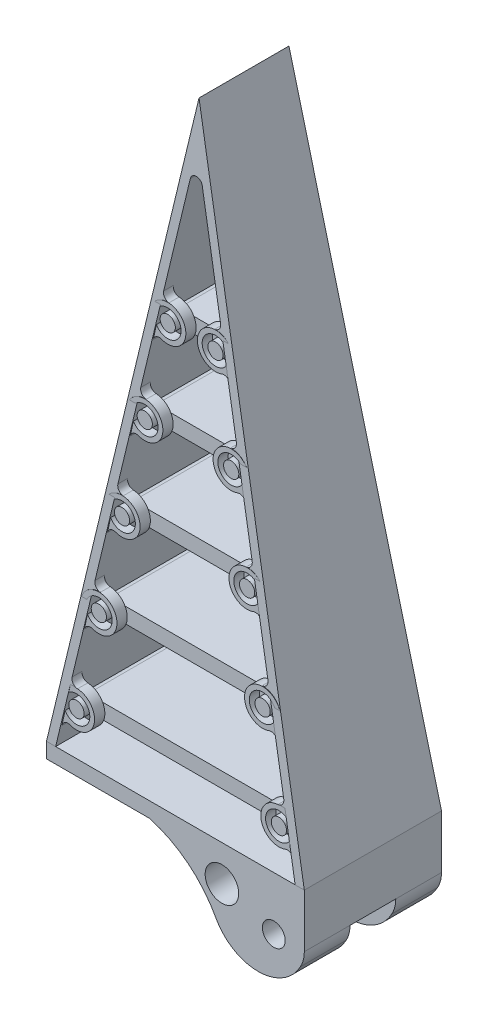
SolidWorks part; units mm, degrees
ref_plane "Ebene vorne" through (0, 0, 0) normal (0, 0, 1) x (1, 0, 0)
ref_plane "Ebene oben" through (0, 0, 0) normal (0, 1, 0) x (1, 0, 0)
ref_plane "Ebene rechts" through (0, 0, 0) normal (1, 0, 0) x (0, 0, -1)
ref_plane "Ebene7" through (0, 0, 9) normal (0, 0, 1) x (1, 0, 0)
ref_plane "Ebene8" through (17, 0, 0) normal (1, 0, 0) x (0, 0, -1)
sketch "Skizze1" plane through (0, 0, 0) normal (0, 0, 1) x (1, 0, 0)
  line L0 (0, 0) -> (16.9111, -80)
  line L1 (16.9111, -80) -> (15.7111, -80)
  line L2 (15.7111, -80) -> (0, -5.6767)
  line L3 (0, -5.6767) -> (-15.7111, -80)
  line L4 (-15.7111, -80) -> (-16.9111, -80)
  line L5 (-16.9111, -80) -> (0, 0)
  point P2 (-16.3111, -80)
  dimension "D1" = 1.2
  dimension "D2" = 1.2
  dimension "D3" = 23.872
  dimension "D4" = 80
extrude "Aufsatz-Linear austragen4" add sketch "Skizze1" along normal blind 18
sketch "Skizze11" plane through (17, 0, 0) normal (1, 0, 0) x (0, 0, -1)
  line L0 (-18, -80) -> (-14.9, 0)
  line L1 (-18, 0) -> (0, 0) construction
  line L2 (-14.9, 0) -> (-18, 0)
  line L3 (-18, 0) -> (-18, -80)
  line L4 (0, -80) -> (-3.1, 0)
  line L5 (-3.1, 0) -> (0, 0)
  line L6 (0, 0) -> (0, -80)
  dimension "D1" = 3.1
  dimension "D2" = 3.1
extrude "Schnitt-Linear austragen1" cut sketch "Skizze11" against normal through all
sketch "Skizze6" plane through (0, 0, 9) normal (0, 0, 1) x (1, 0, 0)
  line L1 (0, -5.6767) -> (-15.7111, -80) construction
  line L2 (15.7111, -80) -> (0, -5.6767) construction
  line L8 (3.1325, -25.6767) -> (-3.1325, -25.6767)
  line L11 (-3.1325, -27.6767) -> (3.1325, -27.6767)
  arc A0 (-3.1325, -25.6767) -> (-3.1325, -27.6767) centre (-3.1325, -26.6767) ccw
  arc A1 (3.1325, -25.6767) -> (3.1325, -27.6767) centre (3.1325, -26.6767) cw
  point P4 (-4.1325, -26.6767)
  point P9 (4.1325, -26.6767)
  dimension "D3" = 0.3
  dimension "D1" = 20
  dimension "D2" = 2
  dimension "D4" = 0.3
extrude "Aufsatz-Linear austragen5" add sketch "Skizze6" along normal blind 5.37 and the other way blind 5.37
sketch "Skizze7" plane through (0, 0, 9) normal (0, 0, 1) x (1, 0, 0)
  line L9 (5.6692, -37.6767) -> (-5.6692, -37.6767)
  line L12 (-5.6692, -39.6767) -> (5.6692, -39.6767)
  line L13 (-3.1325, -27.6767) -> (3.1325, -27.6767) construction
  line L14 (0, -5.6767) -> (-15.7111, -80) construction
  line L15 (15.7111, -80) -> (0, -5.6767) construction
  arc A0 (-5.6692, -37.6767) -> (-5.6692, -39.6767) centre (-5.6692, -38.6767) ccw
  arc A1 (5.6692, -37.6767) -> (5.6692, -39.6767) centre (5.6692, -38.6767) cw
  point P3 (-6.6692, -38.6767)
  point P10 (6.6692, -38.6767)
  dimension "D3" = 0.3
  dimension "D1" = 10
  dimension "D2" = 2
  dimension "D4" = 0.3
extrude "Aufsatz-Linear austragen6" add sketch "Skizze7" along normal blind 5.85 and the other way blind 5.85
sketch "Skizze8" plane through (0, 0, 9) normal (0, 0, 1) x (1, 0, 0)
  line L9 (8.2059, -49.6767) -> (-8.2059, -49.6767)
  line L12 (-8.2059, -51.6767) -> (8.2059, -51.6767)
  line L13 (-5.6692, -39.6767) -> (5.6692, -39.6767) construction
  line L14 (0, -5.6767) -> (-15.7111, -80) construction
  line L15 (15.7111, -80) -> (0, -5.6767) construction
  arc A0 (-8.2059, -49.6767) -> (-8.2059, -51.6767) centre (-8.2059, -50.6767) ccw
  arc A1 (8.2059, -49.6767) -> (8.2059, -51.6767) centre (8.2059, -50.6767) cw
  point P6 (-9.2059, -50.6767)
  point P11 (9.2059, -50.6767)
  dimension "D3" = 0.3
  dimension "D1" = 10
  dimension "D2" = 2
  dimension "D4" = 0.3
extrude "Aufsatz-Linear austragen7" add sketch "Skizze8" along normal blind 6.3 and the other way blind 6.3
sketch "Skizze9" plane through (0, 0, 9) normal (0, 0, 1) x (1, 0, 0)
  line L9 (10.7426, -61.6767) -> (-10.7426, -61.6767)
  line L12 (-10.7426, -63.6767) -> (10.7426, -63.6767)
  line L13 (-8.2059, -51.6767) -> (8.2059, -51.6767) construction
  line L14 (0, -5.6767) -> (-15.7111, -80) construction
  line L15 (15.7111, -80) -> (0, -5.6767) construction
  arc A0 (-10.7426, -61.6767) -> (-10.7426, -63.6767) centre (-10.7426, -62.6767) ccw
  arc A1 (10.7426, -61.6767) -> (10.7426, -63.6767) centre (10.7426, -62.6767) cw
  point P3 (-11.7426, -62.6767)
  point P10 (11.7426, -62.6767)
  dimension "D3" = 0.3
  dimension "D1" = 10
  dimension "D2" = 2
  dimension "D4" = 0.3
extrude "Aufsatz-Linear austragen8" add sketch "Skizze9" along normal blind 6.8 and the other way blind 6.8
sketch "Skizze10" plane through (0, 0, 9) normal (0, 0, 1) x (1, 0, 0)
  line L9 (13.2792, -73.6767) -> (-13.2792, -73.6767)
  line L12 (-13.2792, -75.6767) -> (13.2792, -75.6767)
  line L13 (-10.7426, -63.6767) -> (10.7426, -63.6767) construction
  line L14 (0, -5.6767) -> (-15.7111, -80) construction
  line L15 (15.7111, -80) -> (0, -5.6767) construction
  arc A0 (-13.2792, -73.6767) -> (-13.2792, -75.6767) centre (-13.2792, -74.6767) ccw
  arc A1 (13.2792, -73.6767) -> (13.2792, -75.6767) centre (13.2792, -74.6767) cw
  point P3 (-14.2792, -74.6767)
  point P10 (14.2792, -74.6767)
  dimension "D3" = 0.3
  dimension "D1" = 10
  dimension "D2" = 2
  dimension "D4" = 0.3
extrude "Aufsatz-Linear austragen9" add sketch "Skizze10" along normal blind 7.2 and the other way blind 7.2
sketch "Skizze13" plane through (0, 0, 14.37) normal (0, 0, 1) x (1, 0, 0)
  circle A0 centre (-3.1325, -26.6767) radius 1
  circle A1 centre (3.1325, -26.6767) radius 1
  dimension "D1" = 2
  dimension "D2" = 2
extrude "Aufsatz-Linear austragen12" add sketch "Skizze13" along normal blind 1.5
sketch "Skizze15" plane through (0, 0, 15.3) normal (0, 0, 1) x (1, 0, 0)
  circle A0 centre (-8.2059, -50.6767) radius 1
  circle A1 centre (8.2059, -50.6767) radius 1
extrude "Aufsatz-Linear austragen14" add sketch "Skizze15" along normal blind 1.5
sketch "Skizze14" plane through (0, 0, 14.85) normal (0, 0, 1) x (1, 0, 0)
  circle A0 centre (-5.6692, -38.6767) radius 1
  circle A1 centre (5.6692, -38.6767) radius 1
extrude "Aufsatz-Linear austragen13" add sketch "Skizze14" along normal blind 1.5
sketch "Skizze16" plane through (0, 0, 15.8) normal (0, 0, 1) x (1, 0, 0)
  circle A0 centre (-10.7426, -62.6767) radius 1
  circle A1 centre (10.7426, -62.6767) radius 1
extrude "Aufsatz-Linear austragen15" add sketch "Skizze16" along normal blind 1.5
sketch "Skizze17" plane through (0, 0, 16.2) normal (0, 0, 1) x (1, 0, 0)
  circle A0 centre (-13.2792, -74.6767) radius 1
  circle A1 centre (13.2792, -74.6767) radius 1
extrude "Aufsatz-Linear austragen16" add sketch "Skizze17" along normal blind 1.5
sketch "Skizze18" plane through (0, 0, 3.63) normal (0, 0, -1) x (-1, 0, 0)
  circle A0 centre (-3.1325, -26.6767) radius 1
  circle A1 centre (3.1325, -26.6767) radius 1
extrude "Aufsatz-Linear austragen17" add sketch "Skizze18" along normal blind 1.5
sketch "Skizze19" plane through (0, 0, 3.15) normal (0, 0, -1) x (-1, 0, 0)
  circle A0 centre (-5.6692, -38.6767) radius 1
  circle A1 centre (5.6692, -38.6767) radius 1
extrude "Aufsatz-Linear austragen18" add sketch "Skizze19" along normal blind 1.5
sketch "Skizze20" plane through (0, 0, 2.7) normal (0, 0, -1) x (-1, 0, 0)
  circle A0 centre (-8.2059, -50.6767) radius 1
  circle A1 centre (8.2059, -50.6767) radius 1
extrude "Aufsatz-Linear austragen19" add sketch "Skizze20" along normal blind 1.5
sketch "Skizze21" plane through (0, 0, 2.2) normal (0, 0, -1) x (-1, 0, 0)
  circle A0 centre (-10.7426, -62.6767) radius 1
  circle A1 centre (10.7426, -62.6767) radius 1
extrude "Aufsatz-Linear austragen20" add sketch "Skizze21" along normal blind 1.5
sketch "Skizze22" plane through (0, 0, 1.8) normal (0, 0, -1) x (-1, 0, 0)
  circle A0 centre (-13.2792, -74.6767) radius 1
  circle A1 centre (13.2792, -74.6767) radius 1
extrude "Aufsatz-Linear austragen21" add sketch "Skizze22" along normal blind 1.5
sketch "Skizze24" plane through (0, 0, 15.87) normal (0, 0, 1) x (1, 0, 0)
  circle A0 centre (-3.1325, -26.6767) radius 1.75
  circle A1 centre (-3.1325, -26.6767) radius 2.375
  circle A2 centre (3.1325, -26.6767) radius 1.75
  circle A3 centre (3.1325, -26.6767) radius 2.375
  dimension "D1" = 3.5
  dimension "D2" = 4.75
  dimension "D3" = 3.5
  dimension "D4" = 4.75
extrude "Aufsatz-Linear austragen22" add sketch "Skizze24" against normal blind 1.35
sketch "Skizze25" plane through (0, 0, 16.35) normal (0, 0, 1) x (1, 0, 0)
  circle A0 centre (-5.6692, -38.6767) radius 1.75
  circle A1 centre (-5.6692, -38.6767) radius 2.375
  circle A2 centre (5.6692, -38.6767) radius 1.75
  circle A3 centre (5.6692, -38.6767) radius 2.375
  dimension "D1" = 3.5
  dimension "D2" = 4.75
  dimension "D3" = 3.5
  dimension "D4" = 4.75
extrude "Aufsatz-Linear austragen23" add sketch "Skizze25" against normal blind 1.35
sketch "Skizze26" plane through (0, 0, 16.8) normal (0, 0, 1) x (1, 0, 0)
  circle A0 centre (-8.2059, -50.6767) radius 1.75
  circle A1 centre (-8.2059, -50.6767) radius 2.375
  circle A2 centre (8.2059, -50.6767) radius 1.75
  circle A3 centre (8.2059, -50.6767) radius 2.375
  dimension "D1" = 3.5
  dimension "D2" = 4.75
  dimension "D3" = 3.5
  dimension "D4" = 4.75
extrude "Aufsatz-Linear austragen24" add sketch "Skizze26" against normal blind 1.35
sketch "Skizze27" plane through (0, 0, 17.3) normal (0, 0, 1) x (1, 0, 0)
  circle A0 centre (-10.7426, -62.6767) radius 1.75
  circle A1 centre (-10.7426, -62.6767) radius 2.375
  circle A2 centre (10.7426, -62.6767) radius 1.75
  circle A3 centre (10.7426, -62.6767) radius 2.375
  dimension "D1" = 3.5
  dimension "D2" = 4.75
  dimension "D3" = 3.5
  dimension "D4" = 4.75
extrude "Aufsatz-Linear austragen25" add sketch "Skizze27" against normal blind 1.35
sketch "Skizze28" plane through (0, 0, 17.7) normal (0, 0, 1) x (1, 0, 0)
  circle A0 centre (-13.2792, -74.6767) radius 1.75
  circle A1 centre (-13.2792, -74.6767) radius 2.375
  circle A2 centre (13.2792, -74.6767) radius 1.75
  circle A3 centre (13.2792, -74.6767) radius 2.375
  dimension "D1" = 3.5
  dimension "D2" = 4.75
  dimension "D3" = 3.5
  dimension "D4" = 4.75
extrude "Aufsatz-Linear austragen26" add sketch "Skizze28" against normal blind 1.35
sketch "Skizze29" plane through (0, 0, 2.13) normal (0, 0, -1) x (-1, 0, 0)
  circle A0 centre (-3.1325, -26.6767) radius 1.75
  circle A1 centre (-3.1325, -26.6767) radius 2.375
  circle A2 centre (3.1325, -26.6767) radius 1.75
  circle A3 centre (3.1325, -26.6767) radius 2.375
extrude "Aufsatz-Linear austragen27" add sketch "Skizze29" against normal blind 1.35
sketch "Skizze30" plane through (0, 0, 1.65) normal (0, 0, -1) x (-1, 0, 0)
  circle A0 centre (-5.6692, -38.6767) radius 1.75
  circle A1 centre (-5.6692, -38.6767) radius 2.375
  circle A2 centre (5.6692, -38.6767) radius 1.75
  circle A3 centre (5.6692, -38.6767) radius 2.375
extrude "Aufsatz-Linear austragen28" add sketch "Skizze30" against normal blind 1.35
sketch "Skizze31" plane through (0, 0, 1.2) normal (0, 0, -1) x (-1, 0, 0)
  circle A0 centre (-8.2059, -50.6767) radius 1.75
  circle A1 centre (-8.2059, -50.6767) radius 2.375
  circle A2 centre (8.2059, -50.6767) radius 1.75
  circle A3 centre (8.2059, -50.6767) radius 2.375
extrude "Aufsatz-Linear austragen29" add sketch "Skizze31" against normal blind 1.35
sketch "Skizze32" plane through (0, 0, 0.7) normal (0, 0, -1) x (-1, 0, 0)
  circle A0 centre (-10.7426, -62.6767) radius 1.75
  circle A1 centre (-10.7426, -62.6767) radius 2.375
  circle A2 centre (10.7426, -62.6767) radius 1.75
  circle A3 centre (10.7426, -62.6767) radius 2.375
extrude "Aufsatz-Linear austragen30" add sketch "Skizze32" against normal blind 1.35
sketch "Skizze33" plane through (0, 0, 0.3) normal (0, 0, -1) x (-1, 0, 0)
  circle A0 centre (-13.2792, -74.6767) radius 1.75
  circle A1 centre (-13.2792, -74.6767) radius 2.375
  circle A2 centre (13.2792, -74.6767) radius 1.75
  circle A3 centre (13.2792, -74.6767) radius 2.375
extrude "Aufsatz-Linear austragen31" add sketch "Skizze33" against normal blind 1.35
fillet "Verrundung1" radius 0.8 1 edges at (0, -5.6767, 9)
fillet "Verrundung2" radius 0.8 40 edges at (12.4073, -64.3707, 16.625) (9.8706, -52.3707, 16.125) (7.3339, -40.3707, 15.675) (4.7973, -28.3707, 15.195) (-4.7973, -28.3707, 15.195) (-7.3339, -40.3707, 15.675) (-9.8706, -52.3707, 16.125) (-12.4073, -64.3707, 16.625) (-14.9439, -76.3707, 17.025) (14.9439, -76.3707, 17.025) (14.116, -72.454, 17.025) (-14.116, -72.454, 17.025) (-11.5793, -60.454, 16.5963) (11.5793, -60.454, 16.5963) (9.0427, -48.454, 16.1138) (-9.0427, -48.454, 16.1138) (-6.506, -36.454, 15.6563) (6.506, -36.454, 15.6563) (3.9693, -24.454, 15.1838) (-3.9693, -24.454, 15.1838) (-7.3339, -40.3707, 2.325) (-4.7973, -28.3707, 2.805) (-3.9693, -24.454, 2.8162) (-6.506, -36.454, 2.3437) (-9.0427, -48.454, 1.8862) (-9.8706, -52.3707, 1.875) (-12.4073, -64.3707, 1.375) (-11.5793, -60.454, 1.4037) (-14.116, -72.454, 0.975) (-14.9439, -76.3707, 0.975) (14.9439, -76.3707, 0.975) (14.116, -72.454, 0.975) (12.4073, -64.3707, 1.375) (11.5793, -60.454, 1.4037) (9.8706, -52.3707, 1.875) (9.0427, -48.454, 1.8862) (7.3339, -40.3707, 2.325) (6.506, -36.454, 2.3437) (4.7973, -28.3707, 2.805) (3.9693, -24.454, 2.8162)
sketch "Skizze37" plane through (0, -80, 0) normal (0, -1, 0) x (1, 0, 0)
  line L0 (-16.9111, 0) -> (-15.7111, 0)
  line L1 (-15.7111, 0) -> (16.9111, 0)
  line L2 (16.9111, 0) -> (16.9111, 18)
  line L3 (16.9111, 18) -> (-16.9111, 18)
  line L4 (-16.9111, 18) -> (-16.9111, 0)
extrude "Aufsatz-Linear austragen32" add sketch "Skizze37" along normal blind 2
sketch "Skizze38" plane through (0, 0, 18) normal (0, 0, 1) x (1, 0, 0)
  line L0 (16.9111, -82) -> (6.7313, -82)
  line L1 (16.9111, -82) -> (16.9111, -87)
  line L2 (16.9111, -82) -> (-16.9111, -82) construction
  line L3 (16.9111, -82) -> (16.9111, -80) construction
  circle A0 centre (12.9111, -87) radius 4
  circle A1 centre (12.9111, -87) radius 1.5
  arc A2 (-3.3949, -82) -> (5.3134, -88.966) centre (-7.2601, -95.7582) cw
  arc A4 (5.3134, -88.966) -> (16.3947, -88.966) centre (10.8541, -85.9729) ccw
  line M6 (-16.9111, -82) -> (16.9111, -82)
  dimension "D1" = 3
  dimension "D2" = 5
  dimension "D3" = 8
extrude "Aufsatz-Linear austragen34" add sketch "Skizze38" against normal blind 18 contours A0 L1 M6 | A0 A1 region at (7.5381, -85.6971, 18) region at (16.6704, -87.9876, 18)
sketch "Skizze39" plane through (0, 0, 18) normal (0, 0, 1) x (1, 0, 0)
  circle A1 centre (12.9111, -87) radius 4
  circle A2 centre (12.9111, -87) radius 1.5 construction
extrude "Schnitt-Linear austragen2" cut sketch "Skizze39" against normal blind 6 from offset 6 offset against normal yes
sketch "Skizze40" plane through (-16.9111, 0, 0) normal (-1, 0, 0) x (0, 0, 1)
  line L7 (12, -93.7115) -> (6, -93.7115)
  line L9 (12, -93.7115) -> (12, -82)
  line L10 (18, -82) -> (0, -82) construction
  line L11 (12, -82) -> (6, -82)
  line L12 (6, -82) -> (6, -93.7115)
extrude "Schnitt-Linear austragen3" cut sketch "Skizze40" against normal blind 33.6
sketch "Skizze41" plane through (0, 0, 0) normal (0, 0, -1) x (-1, 0, 0)
  line L0 (-6.1051, -82) -> (-6.1051, -84.7) construction
  line L1 (3.3949, -82) -> (-6.1051, -82) construction
  circle A0 centre (-6.1051, -84.7) radius 2.2
  dimension "D1" = 4.4
  dimension "D2" = 2.7
  dimension "D3" = 9.5
extrude "Schnitt-Linear austragen4" cut sketch "Skizze41" against normal through all
sketch "Skizze42" plane through (-16.9111, 0, 0) normal (-1, 0, 0) x (0, 0, 1)
  line L0 (8, -82) -> (9, -82)
  line L1 (18, -82) -> (0, -82) construction
  line L3 (9, -82) -> (9, -82.5253)
  line L4 (9, -82.5253) -> (8.82, -82.5253)
  line L5 (8, -82) -> (8, -82.5253)
  line L6 (8, -82.5253) -> (8.18, -82.5253)
  line L7 (8.5, -82) -> (8.5, -82.1718) construction
  arc A0 (8.5, -82.1718) -> (8.82, -82.5253) centre (8.5, -82.4934) cw
  arc A1 (8.5, -82.1718) -> (8.18, -82.5253) centre (8.5, -82.4934) ccw
  point P2 (0, 0)
  point P12 (0, 0)
  point P13 (0, 0)
  point P14 (0, 0)
  point P16 (9, -82)
  dimension "D1" = 1
  dimension "D2" = 0.18
  dimension "D3" = 0.18
extrude "Aufsatz-Linear austragen35" add sketch "Skizze42" against normal blind 25
